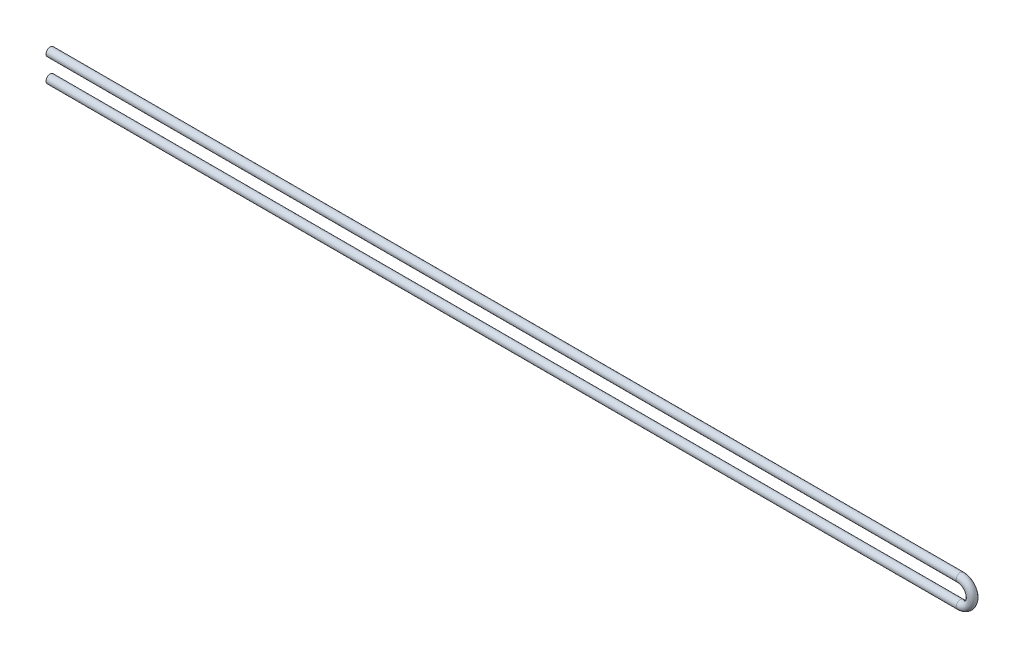
SolidWorks part; units mm, degrees
ref_plane "Front Plane" through (0, 0, 0) normal (0, 0, 1) x (1, 0, 0)
ref_plane "Top Plane" through (0, 0, 0) normal (0, 1, 0) x (1, 0, 0)
ref_plane "Right Plane" through (0, 0, 0) normal (1, 0, 0) x (0, 0, -1)
sketch "Sketch1" plane through (0, 0, 0) normal (0, 0, 1) x (1, 0, 0)
  line L0 (0, 0) -> (2325, 0)
  line L1 (2325, -60) -> (0, -60)
  arc A0 (2325, 0) -> (2325, -60) centre (2325, -30) cw
  dimension "D1" = 2325
  dimension "D2" = 30
sweep "Sweep-Thin1" add path "Sketch1" circular profile diameter 21.3 parameters "D1"=0.5, "D3"=21.3
